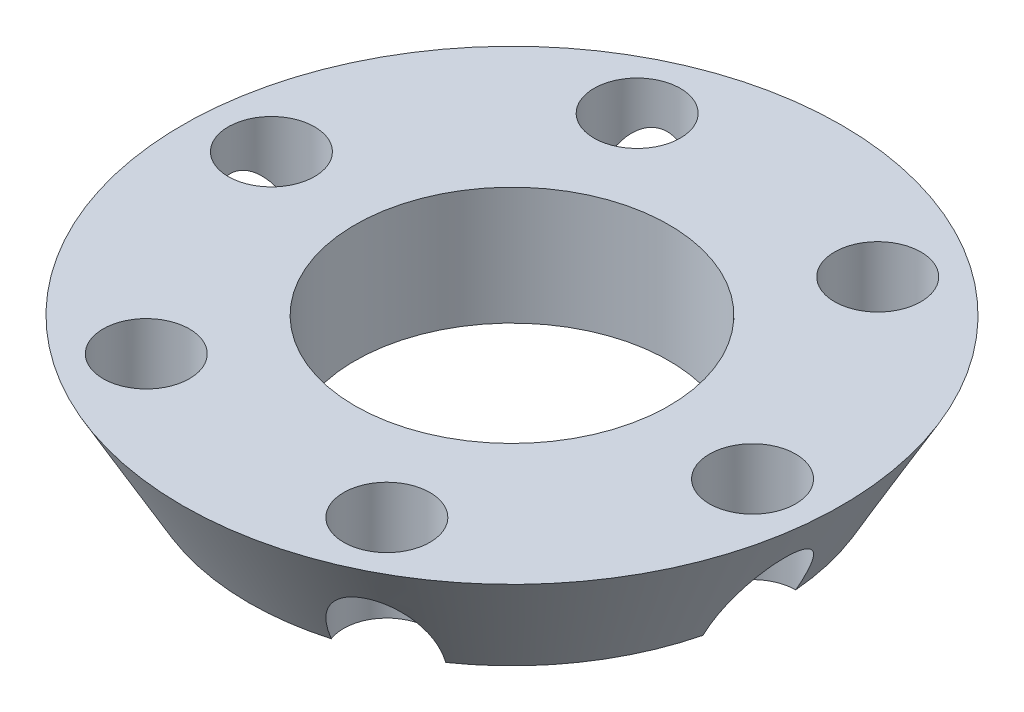
SolidWorks part; units mm, degrees
note: The reader was unsure of these and kept them because the rebuilt part matched: shared geometry of "Sketch1<4>".
ref_plane "Front Plane" through (0, 0, 0) normal (0, 0, 1) x (1, 0, 0)
ref_plane "Top Plane" through (0, 0, 0) normal (0, 1, 0) x (1, 0, 0)
ref_plane "Right Plane" through (0, 0, 0) normal (1, 0, 0) x (0, 0, -1)
sketch "Sketch1" plane through (0, 0, 0) normal (0, 1, 0) x (1, 0, 0)
  circle A0 centre (0, 0) radius 16.75
  circle A1 centre (0, 0) radius 10
  circle A2 centre (0, 0) radius 16.75 construction
  circle A3 centre (-16.6943, 1.3652) radius 2.75
  circle A8 centre (-7.1648, 15.1403) radius 2.75
  circle A9 centre (9.5294, 13.7751) radius 2.75
  circle A10 centre (16.6943, -1.3652) radius 2.75
  circle A11 centre (7.1648, -15.1403) radius 2.75
  circle A12 centre (-9.5294, -13.7751) radius 2.75
  dimension "D1" = 33.5
  dimension "D2" = 33.5
  dimension "D3" = 20
  dimension "D4" = 5.5
  dimension "D5" = 6
ref_plane "Plane1" through (0, 7.5, 0) normal (0, 1, 0) x (1, 0, 0)
sketch "Sketch2" plane through (0, 7.5, 0) normal (0, 1, 0) x (1, 0, 0)
  circle A0 centre (0, 0) radius 21
  dimension "D1" = 42
loft "Loft1" add profiles "Sketch2" section "Sketch1" section "Sketch2" connector at (-16.2185, 0, -4.1859) connector at (-20.5495, 7.5, -4.3266)
extrude "Cut-Extrude1" cut sketch "Sketch1<4>" along normal through all contours A3 | A12 | A9 | A8 | A1 | A11 | A10
sketch "Sketch1<4>" plane through (0, 0, 0) normal (0, 1, 0) x (1, 0, 0) same geometry as "Sketch1"
